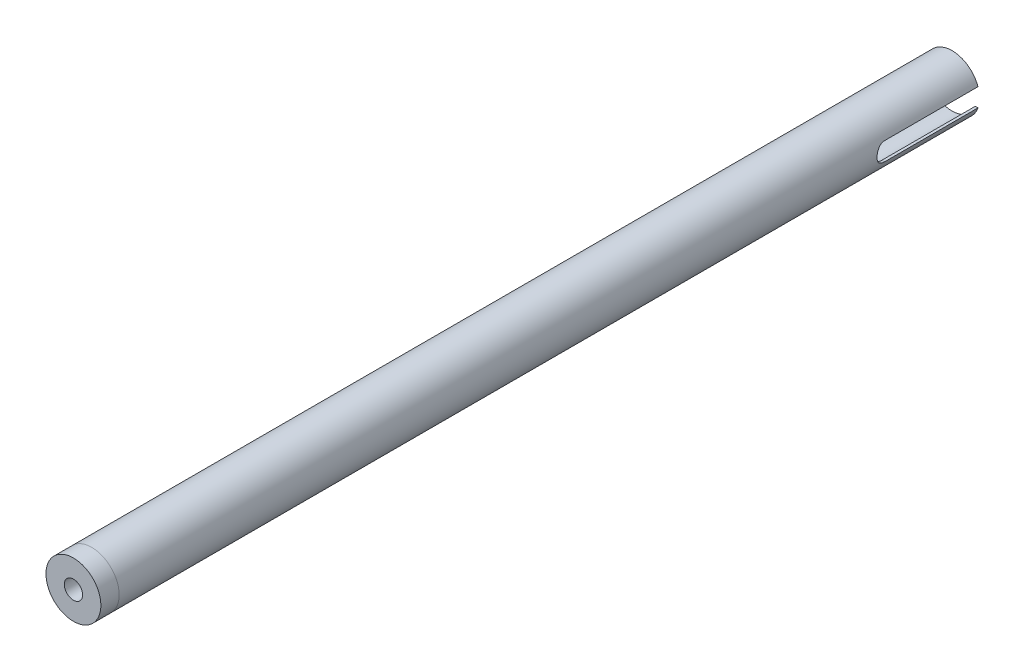
SolidWorks part; units mm, degrees
material "AISI 4130 Steel, normalized at 870C"
ref_plane "Front Plane" through (0, 0, 0) normal (0, 0, 1) x (1, 0, 0)
ref_plane "Top Plane" through (0, 0, 0) normal (0, 1, 0) x (1, 0, 0)
ref_plane "Right Plane" through (0, 0, 0) normal (1, 0, 0) x (0, 0, -1)
sketch "Axis" plane through (0, 0, 0) normal (0, 1, 0) x (1, 0, 0)
  line L0 (0, 0) -> (0, 304.6976) construction
  line L1 (0, 0) -> (0, -21.59) construction
  line L2 (0, 304.6976) -> (-9.525, 304.6976) construction
  line L3 (0, 332.6376) -> (-22.1542, 267.6518) construction
  dimension "D1" = 21.59
  dimension "D2" = 9.525
sketch "Sketch1" plane through (0, 0, 0) normal (0, 0, 1) x (1, 0, 0)
  line L0 (-9.525, 0) -> (9.525, 0) construction
  line L1 (-8.9803, 3.175) -> (8.9803, 3.175)
  line L2 (-8.9803, -3.175) -> (8.9803, -3.175)
  circle A0 centre (0, 0) radius 9.525
  circle A1 centre (0, 0) radius 8.636
  circle A2 centre (0, 0) radius 3.175
  dimension "D1" = 19.05
  dimension "D3" = 6.35
  dimension "D2" = 0.889
  dimension "D4" = 6.35
extrude "Threaded insert 1-1" add sketch "Sketch1" against normal blind 6.35 contours A2 L1 A1 | A1 L1 A0 | A2 L0 A1 L1 | A1 L0 A0 L1 | L0 A1 L2 A0 | L0 A2 L2 A1 | A2 L2 A1 | A1 L2 A0 | L0 A1 L2 A2 | L0 A0 L2 A1 | A0 L0 A1 L1 | A1 L0 A2 L1 region at (5.4259, 1.6615, 0) region at (5.4259, -1.6615, 0) region at (8.8881, 1.6046, 0) region at (8.8881, -1.6046, 0) region at (-5.4259, -1.6615, 0) region at (-5.4259, 1.6615, 0) region at (0, 5.4321, 0) region at (0, -5.4321, 0) region at (0, 8.8265, 0) region at (8.5057, -3.3655, 0) region at (-8.8881, -1.6046, 0) region at (-8.8881, 1.6046, 0)
extrude "Threaded insert 1-2" add sketch "Sketch1<3>" against normal blind 6.35 from surface contours A2 L1 A1 | A2 L0 A1 L1 | L0 A2 L2 A1 | A2 L2 A1 | L0 A1 L2 A2 | A1 L0 A2 L1 region at (5.4259, 1.6615, 0) region at (5.4259, -1.6615, 0) region at (-5.4259, -1.6615, 0) region at (-5.4259, 1.6615, 0) region at (0, 5.4321, 0) region at (0, -5.4321, 0) starting at face at (9.525, 0, -6.35)
sketch "Sketch1<3>" plane through (0, 0, 0) normal (0, 0, 1) x (1, 0, 0) same geometry as "Sketch1"
extrude "A-arm tube" add sketch "Sketch1<4>" against normal up to vertex (304.6976 mm away) from surface separate body contours A1 L1 A0 | A1 L0 A0 L1 | L0 A1 L2 A0 | A1 L2 A0 | L0 A0 L2 A1 | A0 L0 A1 L1 region at (8.8881, 1.6046, 0) region at (8.8881, -1.6046, 0) region at (0, 8.8265, 0) region at (8.5057, -3.3655, 0) region at (-8.8881, -1.6046, 0) region at (-8.8881, 1.6046, 0) up to point (0, 0, -304.6976) starting at face at (8.636, 0, -6.35)
sketch "Sketch1<4>" plane through (0, 0, 0) normal (0, 0, 1) x (1, 0, 0) same geometry as "Sketch1"
extrude "Apex slot" cut sketch "Sketch1<5>" along normal blind 35.56 from surface contours A0 L0 A1 L1 | L0 A0 L2 A1 | A1 L0 A0 L1 | L0 A1 L2 A0 region at (8.8881, 1.6046, 0) region at (8.8881, -1.6046, 0) region at (-8.8881, -1.6046, 0) region at (-8.8881, 1.6046, 0) starting at face at (8.636, 0, -304.6976)
sketch "Sketch1<5>" plane through (0, 0, 0) normal (0, 0, 1) x (1, 0, 0) same geometry as "Sketch1"
fillet "Fillet1" radius 3.175 4 edges at (-8.5057, 3.175, -269.1376) (-8.5057, -3.175, -269.1376) (8.5057, -3.175, -269.1376) (8.5057, 3.175, -269.1376)
equation "\"tube diameter\"= 3 / 4"
equation "\"tube thickness\"= .035"
equation "\"apex thickness\"= .25"
equation "\"tube slot\"= 1.4"
equation "\"D1@Sketch1\"=\"tube diameter\""
equation "\"D2@Sketch1\"=\"tube thickness\""
equation "\"threaded insert hole\"= 1 / 4"
equation "\"D3@Sketch1\"=\"threaded insert hole\""
equation "\"D4@Sketch1\"=\"apex thickness\""
equation "\"D1@Apex slot\" = \"tube slot\""
equation "\"D1@Fillet1\"=\"apex thickness\"/2"
equation "\"D2@Axis\"=\"tube diameter\"/2"
